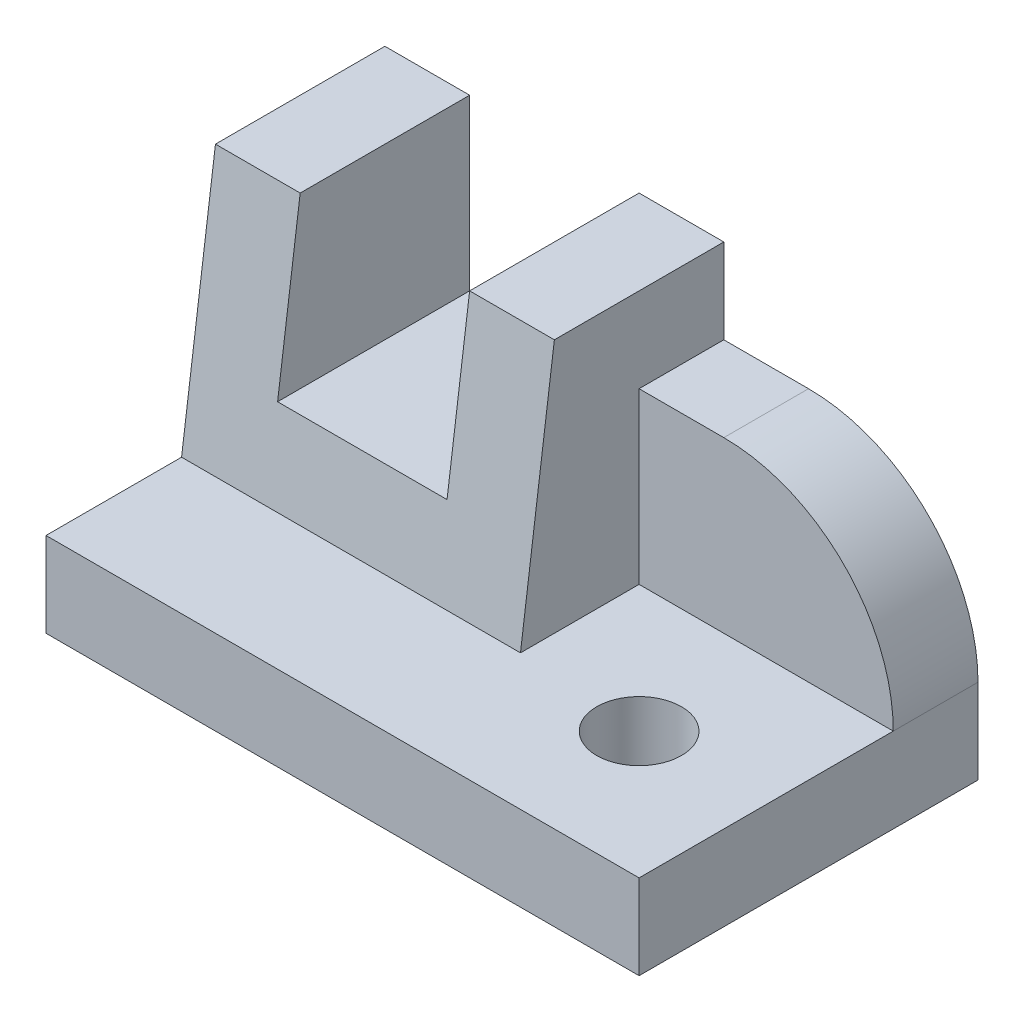
SolidWorks part; units mm, degrees
ref_plane "Front Plane" through (0, 0, 0) normal (0, 0, 1) x (1, 0, 0)
ref_plane "Top Plane" through (0, 0, 0) normal (0, 1, 0) x (1, 0, 0)
ref_plane "Right Plane" through (0, 0, 0) normal (1, 0, 0) x (0, 0, -1)
ref_plane "Plane1" through (0, 0, 0) normal (-1, 0, 0) x (0, -1, 0)
sketch "Sketch1" plane through (0, 0, 0) normal (-1, 0, 0) x (0, -1, 0)
  line L0 (-10, -16) -> (-40, -20)
  line L1 (-40, -20) -> (-10, -20)
  line L2 (-10, -20) -> (-10, -16)
  dimension "D1" = 30
  dimension "Width" = 4
extrude "Boss-Extrude1" add sketch "Sketch1" against normal blind 40
sketch "Sketch2" plane through (0, 0, -20) normal (0, 0, -1) x (-1, 0, 0)
  line L0 (-40, 40) -> (0, 40)
  line L1 (0, 40) -> (0, 10)
  line L2 (0, 10) -> (-40, 10)
  line L3 (-40, 10) -> (-40, 40)
extrude "Boss-Extrude2" add sketch "Sketch2" along normal blind 20
sketch "Sketch3" plane through (40, 0, 0) normal (1, 0, 0) x (0, 0, -1)
  line L0 (40, 10) -> (0, 10)
  line L1 (0, 10) -> (20, 40)
  line L2 (20, 40) -> (40, 40)
  line L3 (40, 40) -> (40, 10)
extrude "Boss-Extrude3" add sketch "Sketch3" along normal blind 30
sketch "Sketch4" plane through (70, 0, 0) normal (1, 0, 0) x (0, 0, -1)
  line L0 (20, 40) -> (0, 10)
  line L1 (0, 10) -> (30, 10)
  line L2 (30, 10) -> (30, 30)
  line L3 (30, 30) -> (40, 30)
  line L4 (40, 30) -> (40, 40)
  line L5 (40, 40) -> (20, 40)
extrude "Cut-Extrude1" cut sketch "Sketch4" against normal blind 30
sketch "Sketch5" plane through (0, 10, 0) normal (0, -1, 0) x (1, 0, 0)
  line L0 (70, 0) -> (70, -40)
  line L1 (70, -40) -> (0, -40)
  line L2 (0, -40) -> (0, 0)
  line L3 (0, 0) -> (70, 0)
extrude "Boss-Extrude4" add sketch "Sketch5" along normal blind 10
sketch "Sketch6" plane through (0, 0, -40) normal (0, 0, -1) x (-1, 0, 0)
  line L0 (-30, 40) -> (-30, 20)
  line L1 (-30, 20) -> (-10, 20)
  line L2 (-10, 20) -> (-10, 40)
  line L3 (-10, 40) -> (-30, 40)
extrude "Cut-Extrude2" cut sketch "Sketch6" against normal through all
hole_wizard "Ø10.0 (10) Diameter Hole1" positions "Sketch8" profile "Sketch7" hole size "Ø10.0" standard "ANSI Metric"
sketch "Sketch8" plane through (0, 0, 0) normal (0, -1, 0) x (-1, 0, 0)
  point P0 (-55, 15)
sketch "Sketch7" plane through (55, 0, -15) normal (1, 0, 0) x (0, 0, -1)
  line L0 (0, 0) -> (0, 40)
  line L1 (0, 40) -> (5, 40)
  line L2 (5, 40) -> (5, 0)
  line L5 (5, 0) -> (0, 0)
  line L11 (0, -6.35) -> (0, 107.95) construction
  dimension "Thru Hole Dia." = 10
  dimension "Thru Hole Depth" = 40
fillet "Fillet1" radius 20 1 edges at (70, 30, -35) tangent propagation no
